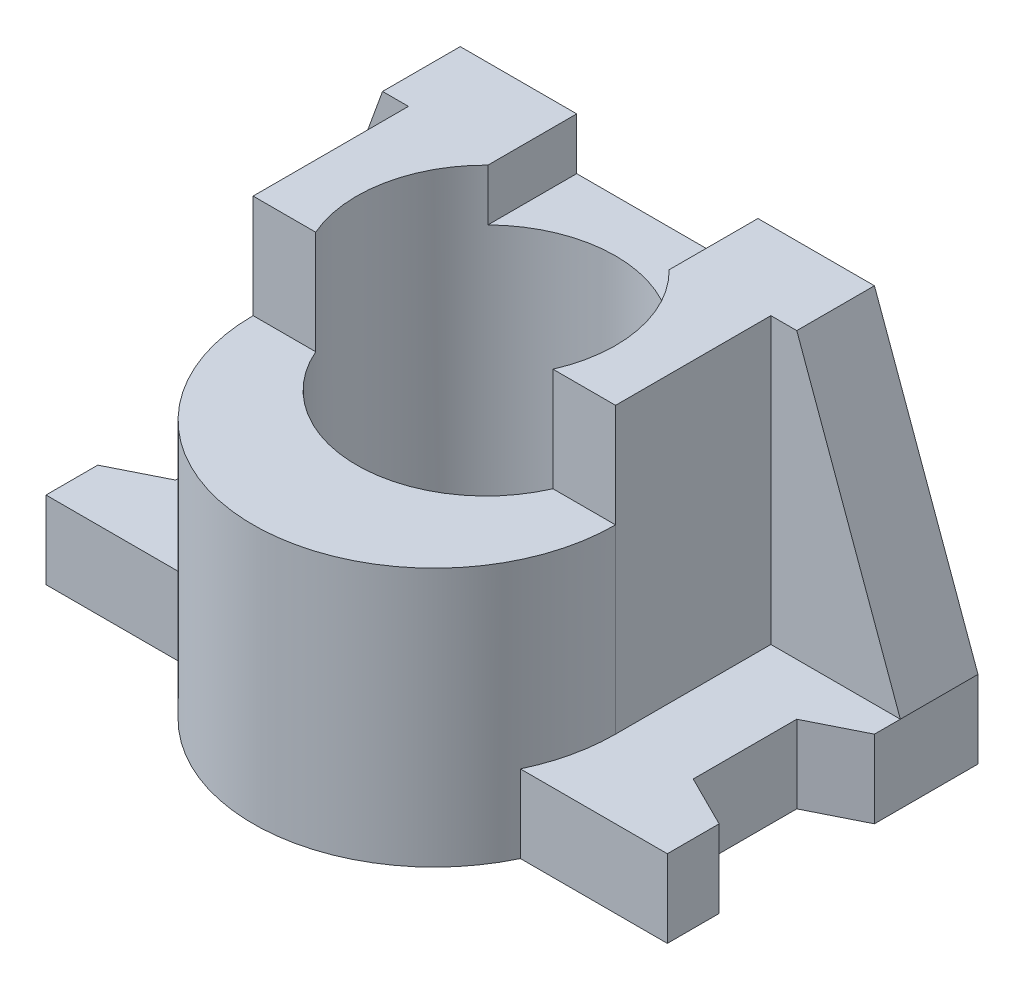
SolidWorks part; units mm, degrees
ref_plane "Front Plane" through (0, 0, 0) normal (0, 0, 1) x (1, 0, 0)
ref_plane "Top Plane" through (0, 0, 0) normal (0, 1, 0) x (1, 0, 0)
ref_plane "Right Plane" through (0, 0, 0) normal (1, 0, 0) x (0, 0, -1)
sketch "Sketch1" plane through (0, 0, 0) normal (0, 1, 0) x (1, 0, 0)
  line L5 (-35, -22.7258) -> (-35, 7.2742)
  line L6 (-35, 22.2742) -> (17.5, 22.2742)
  line L7 (35, 7.2742) -> (35, -22.7258)
  line L8 (-35, 22.2742) -> (-40, 22.2742)
  line L9 (-35, -22.7258) -> (-22.9129, -22.7258)
  line L10 (35, -22.7258) -> (22.9129, -22.7258)
  line L11 (-17.5, 22.2742) -> (-17.5, 5.1277)
  line L12 (-40, 22.2742) -> (-40, 7.2742)
  line L13 (17.5, 22.2742) -> (17.5, 5.1277)
  line L14 (17.5, 22.2742) -> (35, 22.2742)
  line L15 (-40, 7.2742) -> (-35, 7.2742)
  line L16 (0, 22.2742) -> (0, -57.7258) construction
  line L17 (35, 22.2742) -> (40, 22.2742)
  line L18 (40, 22.2742) -> (40, 7.2742)
  line L19 (40, 7.2742) -> (35, 7.2742)
  line L20 (-40, 22.2742) -> (-60, 22.2742)
  line L21 (-60, 22.2742) -> (-60, 2.2742)
  line L22 (-60, -37.7258) -> (-31.6228, -37.7258)
  line L23 (-60, -37.7258) -> (-60, -27.7258)
  line L26 (-50, -22.7258) -> (-60, -27.7258)
  line L27 (-50, -22.7258) -> (-50, -2.7258)
  line L30 (-60, 2.2742) -> (-50, -2.7258)
  line L31 (-60, -27.7258) -> (-60, -37.7258)
  line L32 (60, -37.7258) -> (31.6228, -37.7258)
  line L33 (60, -37.7258) -> (60, -27.7258)
  line L34 (50, -22.7258) -> (60, -27.7258)
  line L35 (50, -22.7258) -> (50, -2.7258)
  line L36 (60, 2.2742) -> (50, -2.7258)
  line L37 (60, 22.2742) -> (60, 2.2742)
  line L38 (40, 22.2742) -> (60, 22.2742)
  arc A0 (-35, -22.7258) -> (35, -22.7258) centre (0, -22.7258) ccw
  circle A1 centre (0, -12.7258) radius 25
extrude "Boss-Extrude1" add sketch "Sketch1" along normal blind 15 contours A0 L5 L15 L12 L20 L21 L30 L27 L26 L23 L22 | A0 L32 L33 L34 L35 L36 L37 L38 L18 L19 L7 region at (-46.2984, 0, 8.458) region at (46.2984, 0, 8.458)
extrude "Boss-Extrude2" add sketch "Sketch1<3>" along normal blind 50 contours L16 A1 L9 A0 | A1 L16 A0 L10 region at (-16.8556, 0, 40.5855) region at (16.8556, 0, 40.5855)
sketch "Sketch1<3>" plane through (0, 0, 0) normal (0, 1, 0) x (1, 0, 0) same geometry as "Sketch1"
extrude "Boss-Extrude3" add sketch "Sketch1<4>" along normal blind 70 contours A1 L11 L6 L8 L12 L15 L5 L9 | A1 L10 L7 L19 L18 L17 L14 L13 region at (-28.7187, 0, -3.7943) region at (28.7187, 0, -3.7943)
sketch "Sketch1<4>" plane through (0, 0, 0) normal (0, 1, 0) x (1, 0, 0) same geometry as "Sketch1"
extrude "Boss-Extrude4" add sketch "Sketch1<5>" along normal blind 60 contours L16 L6 L11 A1 | L6 L16 A1 L13 region at (-9.5714, 0, -15.9849) region at (9.5714, 0, -15.9849)
sketch "Sketch1<5>" plane through (0, 0, 0) normal (0, 1, 0) x (1, 0, 0) same geometry as "Sketch1"
sketch "Sketch3" plane through (0, 0, -22.2742) normal (0, 0, -1) x (-1, 0, 0)
  line L0 (60, 15) -> (40, 15)
  line L1 (40, 15) -> (40, 70)
  line L2 (40, 70) -> (60, 15)
  line L3 (-60, 15) -> (-40, 15)
  line L4 (-40, 15) -> (-40, 70)
  line L5 (-40, 70) -> (-60, 15)
extrude "Boss-Extrude5" add sketch "Sketch3" against normal blind 15
